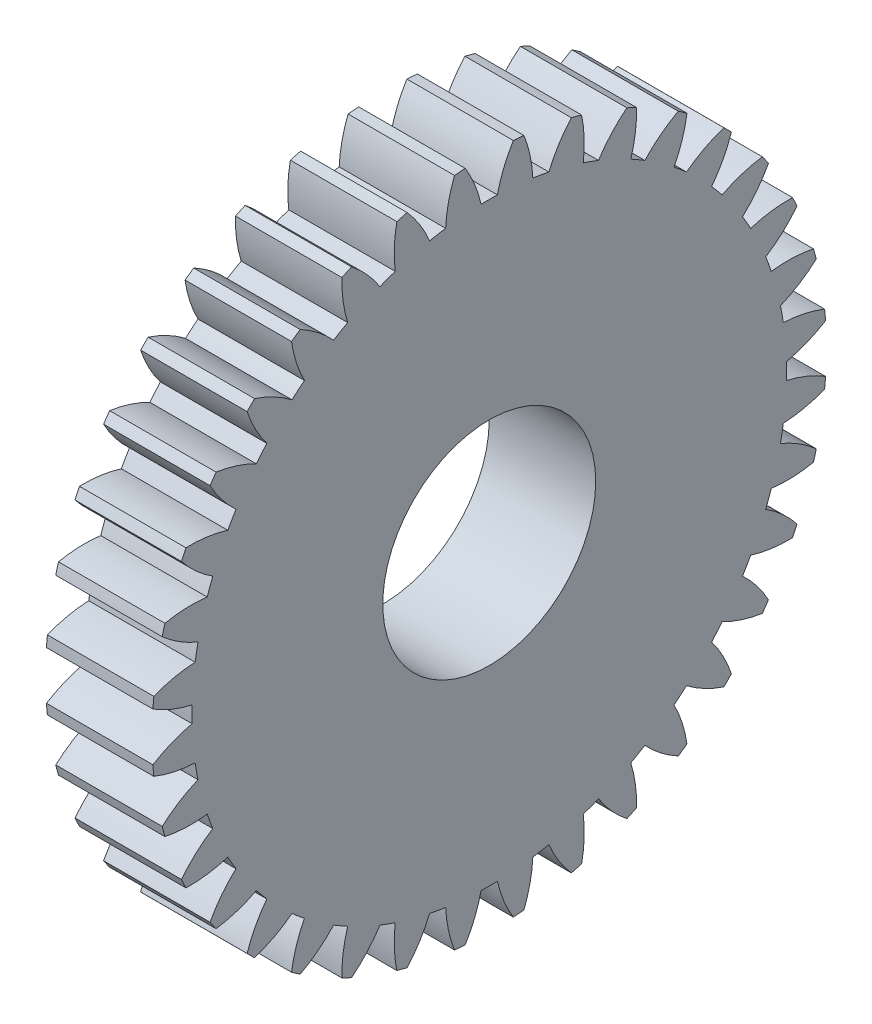
SolidWorks part; units mm, degrees
ref_plane "Plane1" through (0, 0, 0) normal (0, 0, 1) x (1, 0, 0)
ref_plane "Plane2" through (0, 0, 0) normal (0, 1, 0) x (1, 0, 0)
ref_plane "Plane3" through (0, 0, 0) normal (1, 0, 0) x (0, 0, -1)
other "Configuration Table"
sketch "HoldingSke" plane through (0, 0, 0) normal (0, 1, 0) x (1, 0, 0)
  line L0 (0, 0) -> (493.1768, -358.3139)
  line L1 (-15, 0) -> (100, 0) construction
  line L2 (0, 0) -> (-2.1039, 2.3779)
  line L3 (0, 0) -> (-11.863, 4.5341)
  line L4 (0, 0) -> (6.9867, 5.0761)
  line L5 (0, 0) -> (-47.5972, -17.7524)
  line L6 (0, 0) -> (-5.2639, -3.5516)
  line L7 (-2.1039, 2.3779) -> (8.8308, 51.9871)
  line L8 (-76.2, 54.61) -> (-54.9402, 54.61)
  line L9 (-71.009, 38.7566) -> (-53.1078, 45.2721)
  line L10 (-76.2, 71.12) -> (104.1128, 71.12)
  line L11 (0, 0) -> (-6.35, 0)
  line L12 (-76.2, 101.6) -> (-76.1573, 101.6)
  line L13 (24.9733, 27.94) -> (52.9518, 28.4284)
  line L14 (24.9733, 27.94) -> (25.0241, 27.9398)
  line L15 (24.9733, 27.94) -> (100.4021, 29.52)
  circle A0 centre (0, 0) radius 9.525
  circle A1 centre (0, 0) radius 17.7292
  circle A2 centre (0, 0) radius 38.1
  circle A3 centre (0, 0) radius 9.525
  dimension "Num_teeth" = 36
  dimension "H" = 19.05
  dimension "Pitch_radius" = 180.3128
  dimension "Width" = 6.35
  dimension "Thickness" = 6.35
sketch "BasProSke" plane through (0, 0, 0) normal (0, 1, 0) x (1, 0, 0)
  line L0 (-10, 0) -> (60, 0) construction
  line L1 (0, 0) -> (0, 20.1083)
  line L2 (0, 0) -> (6.35, 0)
  line L3 (6.35, 0) -> (6.35, 20.1083)
  line L4 (6.35, 20.1083) -> (0, 20.1083)
  dimension "Thickness" = 6.35
  dimension "Diameter" = 40.2167
revolve "Base-Revolve" add sketch "BasProSke" angle 360 about L0
sketch "TooCutSke" plane through (0, 0, 0) normal (1, 0, 0) x (0, 0, -1)
  line L1 (0, 0) -> (0, 107) construction
  line L2 (0, 0) -> (-0.9056, 19.0285) construction
  line L3 (0, 0) -> (-3.318, 37.9251) construction
  line L4 (-0.9056, 19.0285) -> (-1.659, 18.9625) construction
  arc A0 (0.4859, 17.7225) -> (-0.4859, 17.7225) centre (0, 0) ccw
  arc A1 (1.4524, 20.0813) -> (-1.4524, 20.0813) centre (0, 0) ccw
  circle A2 centre (0, 0) radius 19.05 construction
  circle A3 centre (0, 0) radius 17.9011 construction
  arc A4 (-0.4859, 17.7225) -> (-1.4524, 20.0813) centre (-7.9208, 16.0534) ccw
  arc A5 (1.4524, 20.0813) -> (0.4859, 17.7225) centre (7.9208, 16.0534) ccw
extrude "ToothCut" cut sketch "TooCutSke" along normal through all
fillet "Breaks" [suppressed] radius 0.0212 tangent propagation no
fillet "RootFillets" [suppressed] radius 0.2625
pattern_circular "TeethCuts" count 36 every 10 about axis through (-10, 0, 0) along (1, 0, 0) of "ToothCut", "RootFillets", "Breaks"
sketch "HubNeaOneSke" plane through (0, 0, 0) normal (-1, 0, 0) x (0, 0, 1)
  circle A0 centre (0, 0) radius 17.7292
  dimension "Diameter" = 35.4584
extrude "HubNearOne" [suppressed] add sketch "HubNeaOneSke" along normal blind 44.4501
sketch "HubNeaBotSke" plane through (0, 0, 0) normal (-1, 0, 0) x (0, 0, 1)
  circle A0 centre (0, 0) radius 17.7292
  dimension "Diameter" = 35.4584
extrude "HubNearBoth" [suppressed] add sketch "HubNeaBotSke" along normal blind 22.225
ref_plane "FarPln" through (6.35, 0, 0) normal (1, 0, 0) x (0, 0, -1)
sketch "HubFarSke" plane through (6.35, 0, 0) normal (1, 0, 0) x (0, 0, -1)
  circle A0 centre (0, 0) radius 17.7292
  dimension "Diameter" = 35.4584
extrude "HubFar" [suppressed] add sketch "HubFarSke" along normal blind 22.225
sketch "BorSke" plane through (0, 0, 0) normal (1, 0, 0) x (0, 0, -1)
  circle A0 centre (0, 0) radius 9.525
  dimension "Diameter" = 19.05
extrude "Bore" cut sketch "BorSke" along normal mid plane 101.6001
sketch "KeySke" plane through (0, 0, 0) normal (1, 0, 0) x (0, 0, -1)
  line L0 (-2.3813, 0) -> (-2.3813, 11.7348)
  line L1 (-2.3813, 11.7348) -> (2.3813, 11.7348)
  line L2 (2.3813, 11.7348) -> (2.3813, 0)
  line L3 (0, 0) -> (0, 34) construction
  line L4 (-2.3813, 0) -> (2.3813, 0)
  dimension "Width" = 4.7625
extrude "Keyway" [suppressed] cut sketch "KeySke" along normal mid plane 101.6001
pattern_circular "Keyway2" [suppressed] count 2 every 90 about axis through (-10, 0, 0) along (1, 0, 0)
sketch "Sketch1" plane through (6.35, 0, 0) normal (1, 0, 0) x (0, 0, -1)
  circle A0 centre (0, 0) radius 9.525
  circle A1 centre (0, 0) radius 6.35
  dimension "D1" = 19.05
  dimension "D2" = 12.7
extrude "Boss-Extrude1" add sketch "Sketch1" against normal up to surface (6.35 mm away) up to face at (0, 0, -9.525)
equation "' \"Pitch@HoldingSke\" = 4"
equation "' \"Num_teeth@HoldingSke\" = 12"
equation "' \"Ap@HoldingSke\" =  20"
equation "' \"Ap@HoldingSke\" = 20"
equation "' \"Width@HoldingSke\" = 0.5"
equation "' \"Hub_dia@HoldingSke\"= 1"
equation "' \"Hub_dia@HoldingSke\" = 1"
equation "' \"Overall_len@HoldingSke\" = 1.0"
equation "' \"Bore@HoldingSke\" = 0.75"
equation "' \"T_dim@HoldingSke\" = 0.85"
equation "' \"Width@KeySke\" = 0.25"
equation "' \"Show_teeth@HoldingSke\" = 13"
equation "' \"Backlash@HoldingSke\" = 0.009"
equation "' \"Addendum_fac@HoldingSke\" = 1.0"
equation "' \"Dedendum_fac@HoldingSke\" = 1.25"
equation "' \"Dedendum_add@HoldingSke\" = 0.00005"
equation "' \"Clearance_fac@HoldingSke\" = 0.25"
equation "' \"Pitch@HoldingSke\" = 0.5"
equation "' \"Num_teeth@HoldingSke\" = 23"
equation "' \"Show_teeth@HoldingSke\" = 23"
equation "' \"Backlash@HoldingSke\" = 0.0375"
equation "\"Overcut_dia@TooCutSke\" = (\"Num_teeth@HoldingSke\" + 2 * \"Addendum_fac@HoldingSke\") / \"Pitch@HoldingSke\" + 0.002"
equation "\"Pitch_dia@TooCutSke\" = \"Num_teeth@HoldingSke\" / \"Pitch@HoldingSke\""
equation "\"Base_dia@TooCutSke\" = \"Num_teeth@HoldingSke\" / \"Pitch@HoldingSke\" * cos((\"Ap@HoldingSke\"  * 3.14159265 / 180))"
equation "\"Root_dia@TooCutSke\" = (\"Num_teeth@HoldingSke\" + 2) / \"Pitch@HoldingSke\" - 2 * (\"Addendum_fac@HoldingSke\" + \"Dedendum_fac@HoldingSke\") / \"Pitch@HoldingSke\" - \"Dedendum_add@HoldingSke\" * 2"
equation "\"Half_ang@TooCutSke\" = 180 / \"Num_teeth@HoldingSke\""
equation "\"Half_CT@TooCutSke\" = \"Num_teeth@HoldingSke\" / \"Pitch@HoldingSke\" * sin((3.14159265 / 2 / \"Num_teeth@HoldingSke\")) / 2 - 7 * \"Backlash@HoldingSke\" / 4"
equation "\"Flank_rad@TooCutSke\" = \"Num_teeth@HoldingSke\" / \"Pitch@HoldingSke\" / 5"
equation "\"Radius@RootFillets\" = \"Clearance_fac@HoldingSke\" / \"Pitch@HoldingSke\" + \"Dedendum_add@HoldingSke\""
equation "\"Break_rad@Breaks\" = 0.02 / \"Pitch@HoldingSke\""
equation "\"Thickness@HoldingSke\" = \"Width@HoldingSke\""
equation "\"OAL@HoldingSke\" = \"Thickness@HoldingSke\""
equation "\"MHD@HoldingSke\" = (\"Num_teeth@HoldingSke\" + 2) / \"Pitch@HoldingSke\" - 2 * (\"Addendum_fac@HoldingSke\" + \"Dedendum_fac@HoldingSke\")  / \"Pitch@HoldingSke\" - \"Dedendum_add@HoldingSke\" * 2"
equation "\"MBD@HoldingSke\" = (\"Num_teeth@HoldingSke\" + 2) / \"Pitch@HoldingSke\" - 2 * (\"Addendum_fac@HoldingSke\" + \"Dedendum_fac@HoldingSke\")  / \"Pitch@HoldingSke\" - \"Dedendum_add@HoldingSke\" * 2 - 0.002"
equation "\"MHD@HoldingSke\" = ((sgn( \"MHD@HoldingSke\" - \"Hub_dia@HoldingSke\" )-1)*( \"MHD@HoldingSke\" - \"Hub_dia@HoldingSke\" ))/-2+ \"Hub_dia@HoldingSke\""
equation "\"MBD@HoldingSke\" = ((sgn( \"MBD@HoldingSke\" - \"Bore@HoldingSke\" )-1)*( \"MBD@HoldingSke\" - \"Bore@HoldingSke\" ))/-2+ \"Bore@HoldingSke\""
equation "\"OAL@HoldingSke\" = ((sgn( \"OAL@HoldingSke\" - \"Overall_len@HoldingSke\" )+1)*( \"OAL@HoldingSke\" - \"Overall_len@HoldingSke\" ))/2 + \"Overall_len@HoldingSke\" + 0.000002"
equation "\"Num_teeth@TeethCuts\" = int( \"Show_teeth@HoldingSke\" ) + 1"
equation "\"Num_teeth@TeethCuts\" = ((sgn( \"Num_teeth@TeethCuts\" - \"Num_teeth@HoldingSke\" )-1)*( \"Num_teeth@TeethCuts\" - \"Num_teeth@HoldingSke\" ))/-2+ \"Num_teeth@HoldingSke\""
equation "\"Num_teeth@TeethCuts\" = ((sgn( \"Num_teeth@TeethCuts\" - 2.0)+1)*( \"Num_teeth@TeethCuts\" - 2.0))/2 +2.0"
equation "\"Angle@TeethCuts\" = 360.0 / \"Num_teeth@HoldingSke\""
equation "\"Diameter@BasProSke\" = (\"Num_teeth@HoldingSke\" + 2 * \"Addendum_fac@HoldingSke\") / \"Pitch@HoldingSke\""
equation "\"Thickness@BasProSke\"  = \"Thickness@HoldingSke\""
equation "' \"Fillet_rad@BasProSke\" =  \"Thickness@HoldingSke\" * 0.05"
equation "' \"Fillet_rad@BasProSke\" = \"Thickness@HoldingSke\" * 0.05"
equation "\"MHD@HoldingSke\" = ((sgn( \"MHD@HoldingSke\" - \"Root_dia@TooCutSke\" )-1)*( \"MHD@HoldingSke\" - \"Root_dia@TooCutSke\" ))/-2+ \"Root_dia@TooCutSke\""
equation "\"Diameter@HubNeaOneSke\" = \"MHD@HoldingSke\""
equation "\"Length@HubNearOne\" = \"OAL@HoldingSke\" - \"Thickness@BasProSke\""
equation "\"Diameter@HubNeaBotSke\" = \"MHD@HoldingSke\""
equation "\"Length@HubNearBoth\" = ( \"OAL@HoldingSke\" - \"Thickness@BasProSke\" ) / 2.0"
equation "\"Thickness@FarPln\" = \"Thickness@BasProSke\""
equation "\"Diameter@HubFarSke\" = \"MHD@HoldingSke\""
equation "\"Length@HubFar\" = ( \"OAL@HoldingSke\" - \"Thickness@BasProSke\" ) / 2.0"
equation "\"Diameter@BorSke\" = \"MBD@HoldingSke\""
equation "\"D1@Bore\" = \"OAL@HoldingSke\" * 2.0"
equation "\"D1@Keyway\" = \"OAL@HoldingSke\" * 2.0"
equation "\"Offset@KeySke\" = \"T_dim@HoldingSke\" - \"MBD@HoldingSke\" / 2.0"
